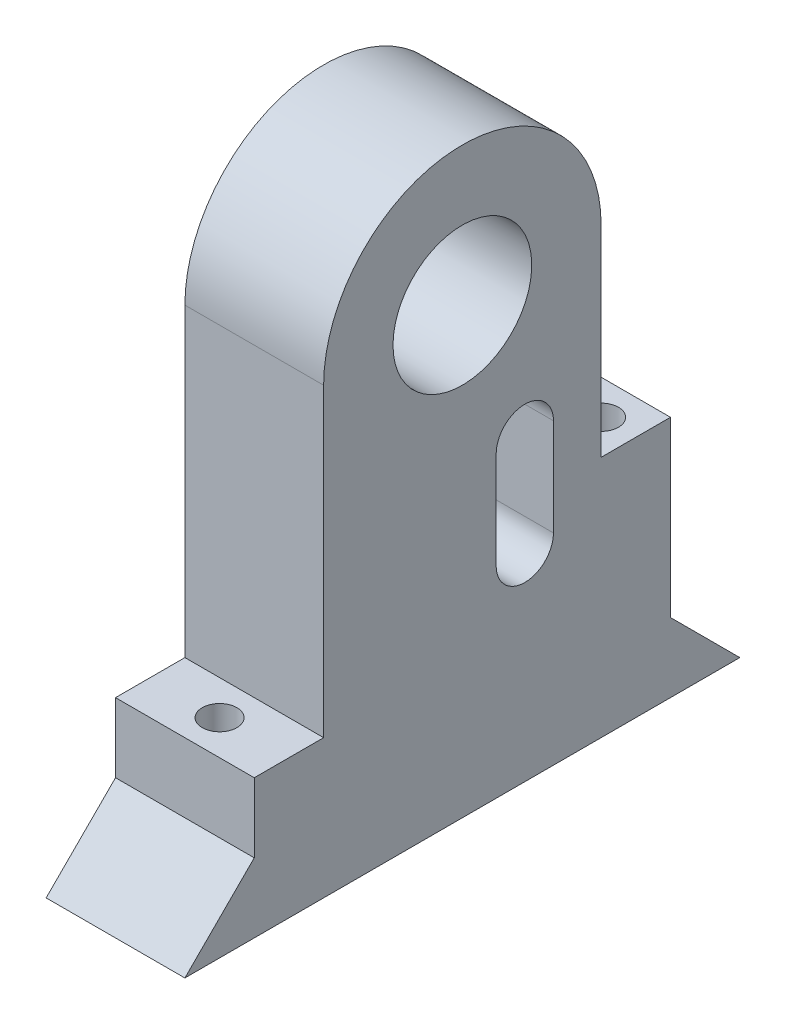
SolidWorks part; units mm, degrees
ref_plane "Front Plane" through (0, 0, 0) normal (0, 0, 1) x (1, 0, 0)
ref_plane "Top Plane" through (0, 0, 0) normal (0, 1, 0) x (1, 0, 0)
ref_plane "Right Plane" through (0, 0, 0) normal (1, 0, 0) x (0, 0, -1)
sketch "Sketch1" plane through (0, 0, 0) normal (1, 0, 0) x (0, 0, -1)
  line L0 (10, 0) -> (-10, 0)
  line L1 (-10, 10) -> (-10, 32)
  line L2 (0, 42) -> (0, 0) construction
  line L3 (20, 0) -> (10, 0)
  line L4 (10, 17.5) -> (10, 32)
  line L5 (15, 10) -> (15, 5)
  line L6 (-15, 5) -> (-20, 0)
  line L7 (-15, 10) -> (-15, 5)
  line L8 (-20, 0) -> (-10, 0)
  line L10 (15, 5) -> (20, 0)
  line L11 (-15, 10) -> (-10, 10)
  line L12 (15, 10) -> (15, 17.5)
  line L13 (15, 17.5) -> (10, 17.5)
  arc A0 (-10, 32) -> (10, 32) centre (0, 32) cw
  dimension "D1" = 10
extrude "Boss-Extrude1" add sketch "Sketch1" along normal blind 10 contours A0 L4 L13 L12 L5 L10 L3 L0 L8 L6 L7 L11 L1
sketch "Sketch3" plane through (0, 0, 0) normal (-1, 0, 0) x (0, 0, 1)
  line L0 (-10, 32) -> (10, 32) construction
  line L1 (0, 32) -> (0, 0) construction
hole_wizard "Ø10.0mm Dowel Hole1" positions "3DSketch2" profile "Sketch4" hole size "Ø10.0" standard "ISO"
sketch3d "3DSketch2"
  point P0 (0, 32, 0)
sketch "Sketch4" plane through (0, 32, 0) normal (0, 1, 0) x (0, 0, 1)
  line L0 (0, 0) -> (0, 28.0043)
  line L1 (0, 28.0043) -> (5, 25)
  line L2 (5, 25) -> (5, 0)
  line L5 (5, 0) -> (0, 0)
  line L10 (0, 28.0043) -> (-5, 25) construction
  line L11 (0, -6.35) -> (0, 107.95) construction
  dimension "Hole Dia." = 10
  dimension "Hole Depth" = 25
  dimension "Drill Angle" = 118
sketch "Sketch5" plane through (10, 0, 0) normal (1, 0, 0) x (0, 0, -1)
  line L0 (0, 32) -> (10, 32) construction
  line L1 (10, 32) -> (-10, 32) construction
  line L2 (20, 0) -> (-20, 0) construction
  line L5 (4.5, 21.5) -> (4.5, 14.5) construction
  line L6 (6.5636, 21.5) -> (6.5636, 14.5)
  line L7 (2.4364, 21.5) -> (2.4364, 14.5)
  arc A0 (6.5636, 21.5) -> (2.4364, 21.5) centre (4.5, 21.5) ccw
  arc A1 (2.4364, 14.5) -> (6.5636, 14.5) centre (4.5, 14.5) ccw
  point P9 (4.5, 18)
  dimension "D1" = 18
extrude "Cut-Extrude1" cut sketch "Sketch5" against normal blind 10
sketch "Sketch6" plane through (0, 0, 0) normal (0, -1, 0) x (-1, 0, 0)
  line L0 (-2.5, -10) -> (-2.5, 10) construction
  line L1 (-5, -10) -> (0, -10) construction
  line L2 (-5, 10) -> (0, 10) construction
sketch "Sketch7" plane through (0, 0, 0) normal (0, -1, 0) x (-1, 0, 0)
  line L0 (0, 0) -> (-10, 0) construction
  line L1 (-10, 20) -> (-10, -20) construction
  line L2 (-5, 0) -> (-5, 5) construction
  line L3 (-5, 0) -> (-5, -5) construction
  dimension "D1" = 5
  dimension "D2" = 5
sketch "Sketch8" plane through (0, 10, 0) normal (0, 1, 0) x (1, 0, 0)
  line L0 (2.5, 10) -> (2.5, 15) construction
  line L1 (5, 10) -> (0, 10) construction
  line L2 (5, 15) -> (0, 15) construction
  line L3 (2.5, 12.5) -> (0, 12.5) construction
  line L4 (0, 15) -> (0, 10) construction
  line L5 (5, -15) -> (5, -10) construction
  line L6 (10, -15) -> (0, -15) construction
  line L7 (10, -10) -> (0, -10) construction
  line L8 (5, -12.5) -> (0, -12.5) construction
  line L9 (0, -15) -> (0, -10) construction
hole_wizard "M3 Tapped Hole1" positions "Sketch10" profile "Sketch9" tap size "M3" standard "ISO"
sketch "Sketch10" plane through (0, 10, 0) normal (0, 1, 0) x (1, 0, 0)
  point P0 (5, -12.5)
  point P3 (2.5, 12.5)
sketch "Sketch9" plane through (5, 10, 12.5) normal (1, 0, 0) x (0, 0, 1)
  line L0 (0, 0) -> (0, 18.2511)
  line L1 (0, 18.2511) -> (1.25, 17.5)
  line L2 (1.25, 17.5) -> (1.25, 0)
  line L5 (1.25, 0) -> (0, 0)
  line L10 (0, 18.2511) -> (-1.25, 17.5) construction
  line L11 (0, -6.35) -> (0, 107.95) construction
  dimension "Tap Drill Dia." = 2.5
  dimension "Tap Drill Depth" = 17.5
  dimension "Drill Angle" = 118
sketch "Sketch11" plane through (0, 17.5, 0) normal (0, 1, 0) x (1, 0, 0)
  line L0 (0, 10) -> (0, 12.5) construction
  line L1 (0, 15) -> (0, 10) construction
  line L2 (0, 12.5) -> (10, 12.5) construction
  line L3 (10, 15) -> (10, 10) construction
  line L4 (10, 12.5) -> (5, 12.5) construction
sketch "Sketch14" plane through (0, 17.5, 0) normal (0, 1, 0) x (1, 0, 0)
  line L0 (10, 12.5) -> (5, 12.5) construction
  line L1 (10, 15) -> (10, 10) construction
  line L2 (7.5, 12.5) -> (7.5, 10) construction
  line L3 (10, 10) -> (0, 10) construction
hole_wizard "M3 Tapped Hole3" positions "Sketch16" profile "Sketch15" tap size "M3" standard "ISO"
sketch "Sketch16" plane through (0, 17.5, 0) normal (0, 1, 0) x (1, 0, 0)
  point P0 (7.5, 12.5)
sketch "Sketch15" plane through (7.5, 17.5, -12.5) normal (1, 0, 0) x (0, 0, 1)
  line L0 (0, 0) -> (0, 28.2511)
  line L1 (0, 28.2511) -> (1.25, 27.5)
  line L2 (1.25, 27.5) -> (1.25, 0)
  line L5 (1.25, 0) -> (0, 0)
  line L10 (0, 28.2511) -> (-1.25, 27.5) construction
  line L11 (0, -6.35) -> (0, 107.95) construction
  dimension "Tap Drill Dia." = 2.5
  dimension "Tap Drill Depth" = 27.5
  dimension "Drill Angle" = 118
sketch "Sketch17" plane through (0, 17.5, 0) normal (0, 1, 0) x (1, 0, 0)
  line L0 (0, 12.5) -> (5, 12.5) construction
  line L1 (2.5, 12.5) -> (2.5, 15) construction
  line L2 (10, 15) -> (0, 15) construction
hole_wizard "M3 Tapped Hole4" positions "Sketch19" profile "Sketch18" tap size "M3" standard "ISO"
sketch "Sketch19" plane through (0, 17.5, 0) normal (0, 1, 0) x (1, 0, 0)
  point P0 (2.5, 12.5)
sketch "Sketch18" plane through (2.5, 17.5, -12.5) normal (1, 0, 0) x (0, 0, 1)
  line L0 (0, 0) -> (0, 28.2511)
  line L1 (0, 28.2511) -> (1.25, 27.5)
  line L2 (1.25, 27.5) -> (1.25, 0)
  line L5 (1.25, 0) -> (0, 0)
  line L10 (0, 28.2511) -> (-1.25, 27.5) construction
  line L11 (0, -6.35) -> (0, 107.95) construction
  dimension "Tap Drill Dia." = 2.5
  dimension "Tap Drill Depth" = 27.5
  dimension "Drill Angle" = 118
